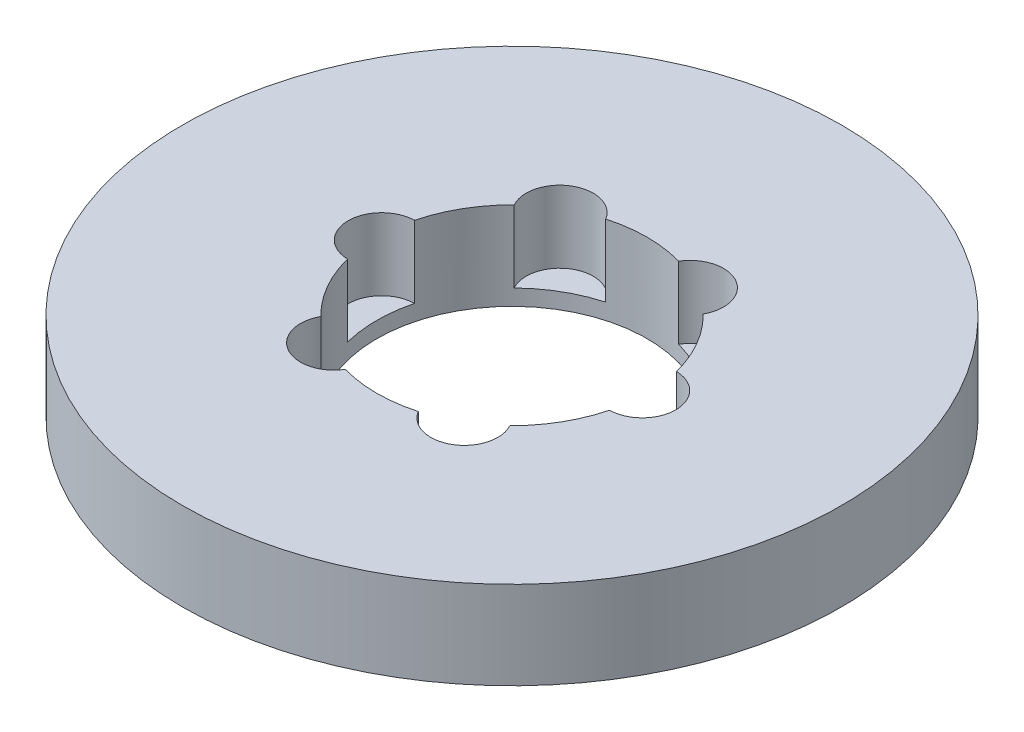
SolidWorks part; units mm, degrees
ref_plane "Front Plane" through (0, 0, 0) normal (0, 0, 1) x (1, 0, 0)
ref_plane "Top Plane" through (0, 0, 0) normal (0, 1, 0) x (1, 0, 0)
ref_plane "Right Plane" through (0, 0, 0) normal (1, 0, 0) x (0, 0, -1)
sketch "Sketch1" plane through (0, 0, 0) normal (0, 1, 0) x (1, 0, 0)
  circle A0 centre (0, 0) radius 97.5
  dimension "FLANGE_OD" = 195
extrude "Boss-Extrude1" add sketch "Sketch1" along normal blind 26
sketch "Sketch2" plane through (0, 0, 0) normal (0, 1, 0) x (1, 0, 0)
  circle A0 centre (0, 0) radius 40
  dimension "BORE_D" = 80
extrude "Cut-Extrude1" cut sketch "Sketch2" along normal through all
sketch "Sketch3" plane through (0, 26, 0) normal (0, 1, 0) x (1, 0, 0)
  circle A0 centre (0, 0) radius 38.5573 construction
  circle A1 centre (-38.5573, 0) radius 9.9155
  dimension "BOLT_D" = 19.831
  dimension "BOLT_PCD" = 77.1145
extrude "Cut-Extrude2" cut sketch "Sketch3" against normal blind 21.2893
pattern_circular "CirPattern1" count 6 over 360 about axis through (0, 0, 0) along (0, 1, 0) of "Cut-Extrude2"
